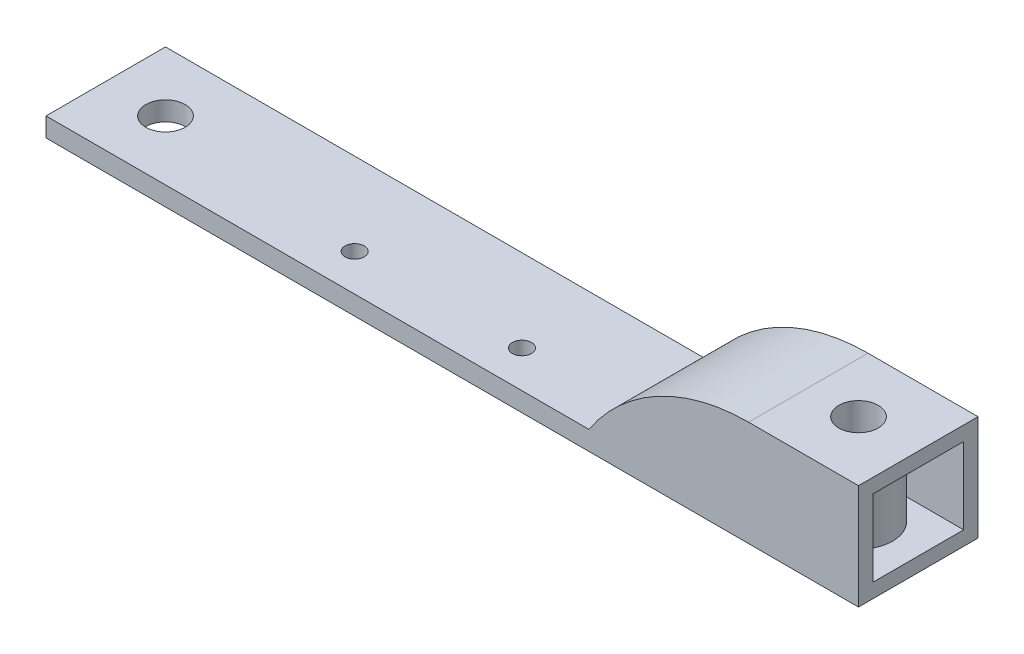
SolidWorks part; units mm, degrees
ref_plane "Front Plane" through (0, 0, 0) normal (0, 0, 1) x (1, 0, 0)
ref_plane "Top Plane" through (0, 0, 0) normal (0, 1, 0) x (1, 0, 0)
ref_plane "Right Plane" through (0, 0, 0) normal (1, 0, 0) x (0, 0, -1)
sketch "Sketch1" plane through (0, 0, 0) normal (0, 1, 0) x (1, 0, 0)
  line L1 (-85, 12.5) -> (85, 12.5)
  line L2 (-85, 12.5) -> (-85, -12.5)
  line L3 (-85, -12.5) -> (85, -12.5)
  line L4 (85, 12.5) -> (85, -12.5)
  line L5 (-85, 12.5) -> (85, -12.5) construction
  line L6 (-85, -12.5) -> (85, 12.5) construction
  circle A0 centre (-10.6801, 3.3392) radius 4.5
  circle A1 centre (-10.6585, -3.6607) radius 14
  circle A2 centre (-28.1585, -4.7634) radius 2
  circle A3 centre (6.8415, -4.7634) radius 2
  circle A4 centre (72.5, 0) radius 4.125
  point P0 (0, 0)
  point P17 (85, 0)
  dimension "D3" = 12.5
  dimension "D4" = 4
  dimension "D5" = 4
  dimension "D6" = 8.25
  dimension "D7" = 7.7366
  dimension "D1" = 25
  dimension "D2" = 170
extrude "Boss-Extrude1" add sketch "Sketch1" along normal blind 4 contours A1 L3 L4 L1 L2 A4 A3 A2 | L3 A1 A0 | A0 region at (0, 0, -10.7817) region at (-10.6556, 0, 2.8007)
sketch "Sketch2" plane through (0, 4, 0) normal (0, 1, 0) x (1, 0, 0)
  line L0 (-85, 12.5) -> (-85, -12.5) construction
  circle A0 centre (-72.5, 0) radius 4.125
  circle A1 centre (-72.5, 0) radius 20 construction
  circle A2 centre (-42.5, 0) radius 10 construction
  dimension "D1" = 8.25
  dimension "D2" = 12.5
extrude "Cut-Extrude1" cut sketch "Sketch2" against normal through all
sketch "Sketch3" plane through (0, 4, 0) normal (0, 1, 0) x (1, 0, 0)
  line L0 (28.5855, 12.5) -> (28.5855, -12.5)
  line L1 (-85, 12.5) -> (85, 12.5) construction
  line L2 (-85, -12.5) -> (85, -12.5) construction
  line L3 (28.5855, -12.5) -> (85, -12.5)
  line L4 (85, -12.5) -> (85, 12.5)
  line L5 (85, 12.5) -> (28.5855, 12.5)
  circle A0 centre (72.5, 0) radius 4.125
extrude "Boss-Extrude2" add sketch "Sketch3" along normal blind 18
sketch "Sketch4" plane through (0, 22, 0) normal (0, 1, 0) x (1, 0, 0)
  line L4 (85, -12.5) -> (85, 12.5)
  line L6 (85, 12.5) -> (60, 12.5)
  line L7 (85, 12.5) -> (28.5855, 12.5) construction
  line L8 (60, 12.5) -> (60, -12.5)
  line L9 (28.5855, -12.5) -> (85, -12.5) construction
  line L10 (60, -12.5) -> (85, -12.5)
  circle A0 centre (72.5, 0) radius 4.125
  dimension "D1" = 25
fillet "Fillet1" radius 40 1 edges at (28.5855, 22, 0)
sketch "Sketch5" plane through (0, 0, 12.5) normal (0, 0, 1) x (1, 0, 0)
  line L0 (85, 19.6943) -> (60.9639, 19.6943)
  line L1 (85, 22) -> (85, 0) construction
  line L2 (32.6181, 4) -> (85, 4)
  line L3 (85, 4) -> (85, 19.6943)
  spline S0 degree 2 poles (32.6181, 4) (45.2561, 17.208) (60.9639, 19.6943) knots 0 0 0 0.765358 0.765358 0.765358
shell "Shell2" thickness 3 removed face at (85, 11, 0)
